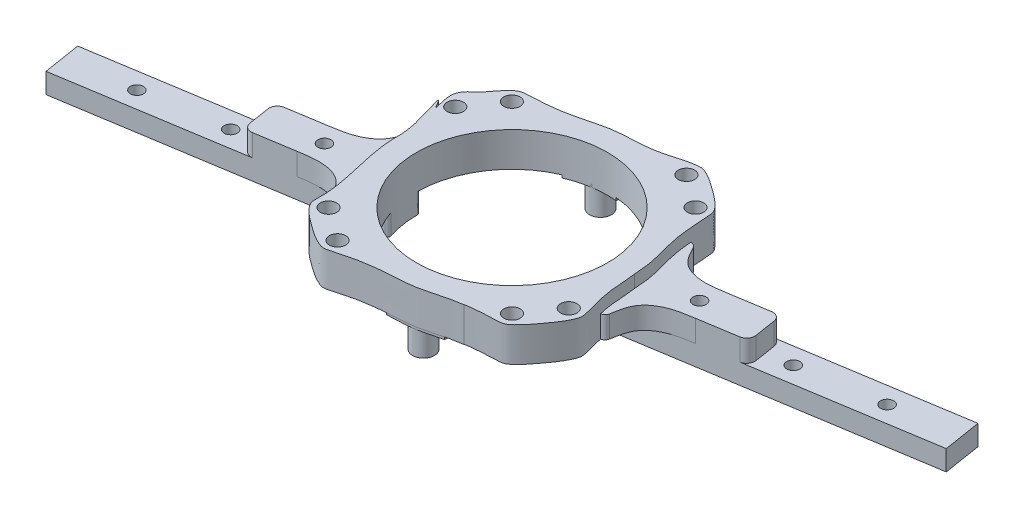
SolidWorks part; units mm, degrees
ref_plane "前视基准面" through (0, 0, 0) normal (0, 0, 1) x (1, 0, 0)
ref_plane "上视基准面" through (0, 0, 0) normal (0, 1, 0) x (1, 0, 0)
ref_plane "右视基准面" through (0, 0, 0) normal (1, 0, 0) x (0, 0, -1)
sketch "草图1" plane through (0, 0, 0) normal (0, 1, 0) x (1, 0, 0)
  circle A0 centre (0, 0) radius 17.5
  circle A1 centre (0, 0) radius 18.901
  dimension "D1" = 35
extrude "凸台-拉伸1" add sketch "草图1" along normal blind 2
sketch "草图2" plane through (0, 0, 0) normal (0, -1, 0) x (1, 0, 0)
  circle A0 centre (-10.7739, 21.1656) radius 1.5
  circle A1 centre (16.8004, 16.7872) radius 1.5
  circle A2 centre (21.1656, 10.7739) radius 1.5
  circle A3 centre (16.7872, -16.8004) radius 1.5
  circle A4 centre (10.7739, -21.1656) radius 1.5
  circle A5 centre (-16.8004, -16.7872) radius 1.5
  circle A6 centre (-21.1656, -10.7739) radius 1.5
  circle A7 centre (-16.7872, 16.8004) radius 1.5
  circle A28 centre (0, 0) radius 17.5
  spline S3 degree 3 poles (11.007, 19.7796) (11.3114, 19.6784) (14.2307, 19.3249) (16.1426, 19.3879) (17.8124, 19.1708) (19.4344, 17.903) (21.2548, 15.4236) (23.0457, 12.9332) (23.7495, 10.9887) (23.274, 8.5261) (21.9734, 4.7628) (22.0269, 1.1873) (21.7447, -0.683) knots 0 0 0 0 0.101498 0.202996 0.236379 0.269761 0.41266 0.555558 0.58894 0.622323 0.811161 1 1 1 1
  spline S4 degree 3 poles (21.7447, -0.683) (21.6101, -1.5752) (21.6055, -3.3542) (20.6884, -6.8809) (19.4904, -11.3054) (19.4855, -15.3122) (19.178, -17.8032) (17.9056, -19.4334) (15.4365, -21.2528) (12.9718, -22.9922) (11.1783, -23.6905) (8.6855, -23.5473) (4.924, -21.9674) (0.2192, -21.8124) (-3.3386, -21.5662) (-6.4463, -20.811) (-9.0785, -20.0903) (-12.7412, -19.4848) (-15.1253, -19.3752) (-17.5836, -19.2474) (-19.4002, -18.127) (-20.9244, -15.1209) (-24.3676, -13.3124) (-22.2966, -7.7817) (-24.7387, -12.2711) (-21.435, -3.3276) (-22.0126, 0.3206) (-20.5515, 8.1406) (-19.1109, 13.0019) (-19.2816, 16.8284) knots 0 0 0 0 0.02817 0.053916 0.112305 0.168269 0.178162 0.188055 0.230405 0.272754 0.280796 0.288838 0.34856 0.404524 0.432694 0.45844 0.502911 0.516855 0.572819 0.576577 0.592462 0.634812 0.677161 0.707499 0.719914 0.775878 0.831843 0.888071 1 1 1 1
  spline S5 degree 3 poles (-19.2816, 16.8284) (-19.323, 17.5174) (-18.1907, 19.2578) (-15.4061, 21.2421) (-12.9273, 23.0421) (-10.9838, 23.7431) (-9.3566, 23.4387) (-7.2233, 22.7077) (-4.4614, 22.2162) (-1.8337, 21.8607) (0.7732, 21.7432) (3.3794, 21.5754) (7.3403, 20.5662) (8.6858, 20.19) (9.8558, 19.9936) (10.7406, 19.8682) (11.007, 19.7796) knots 0 0 0 0 0.047987 0.150696 0.253406 0.277399 0.301393 0.374345 0.447298 0.510152 0.573007 0.641327 0.709648 0.853023 0.882058 1 1 1 1
  dimension "D1" = 3
extrude "凸台-拉伸2" add sketch "草图2" along normal blind 4.3 and the other way blind 2
sketch "草图3" plane through (0, -4.3, 0) normal (0, -1, 0) x (1, 0, 0)
  line L0 (8.3212, 9.3102) -> (-43.6069, 17.5558) construction
  line L1 (3.0581, 19.2587) -> (0, 0) construction
  line L2 (0, 0) -> (-3.0579, -19.2577) construction
  line L3 (-8.4247, -9.2928) -> (43.5035, -17.5384) construction
  circle A0 centre (3.0581, 19.2587) radius 2
  circle A1 centre (3.0581, 19.2587) radius 9 construction
  circle A2 centre (-3.0579, -19.2577) radius 2
  circle A3 centre (-3.0579, -19.2577) radius 9 construction
  dimension "D1" = 18
  dimension "D2" = 4
  dimension "D3" = 18
  dimension "D4" = 4
extrude "凸台-拉伸3" add sketch "草图3" along normal blind 5
sketch "草图5" plane through (0, -4.3, 0) normal (0, -1, 0) x (1, 0, 0)
  line L0 (0, 0) -> (38.9853, -6.1904) construction
  line L1 (70.6703, -14.0546) -> (-71.5479, 8.5279) construction
  circle A0 centre (3.0581, 19.2587) radius 5 construction
  arc A1 (-1.5944, 17.4272) -> (6.9144, 16.0761) centre (0, 0) cw
  arc A2 (-2.6852, -17.2928) -> (2.7444, 17.2835) centre (0, 0) ccw construction
  arc A3 (-1.3158, 21.6815) -> (-1.5944, 17.4272) centre (3.0581, 19.2587) ccw
  arc A4 (7.9454, 20.3141) -> (6.9144, 16.0761) centre (3.0581, 19.2587) cw
  arc A5 (-7.9672, -20.2075) -> (-6.9144, -16.0761) centre (-3.0581, -19.2587) cw
  arc A6 (-6.9144, -16.0761) -> (1.5944, -17.4272) centre (0, 0) ccw
  arc A7 (1.262, -21.7761) -> (1.5944, -17.4272) centre (-3.0581, -19.2587) ccw
  spline S0 degree 3 poles (-1.3158, 21.6815) (-0.2135, 21.5939) (1.3807, 21.5885) (3.4585, 21.3907) (5.444, 20.9684) (6.9168, 20.5202) (7.9454, 20.3141) knots 0 0 0 0 0.352817 0.508743 0.665414 1 1 1 1
  spline S2 degree 3 poles (-7.9672, -20.2075) (-6.892, -20.4656) (-5.3746, -20.9543) (-3.3377, -21.4099) (-1.319, -21.6234) (0.2201, -21.6535) (1.262, -21.7761) knots 0 0 0 0 0.352817 0.508743 0.665414 1 1 1 1
  dimension "D1" = 10
extrude "凸台-拉伸5" add sketch "草图5" along normal blind 0.5
sketch "草图6" plane through (0, -4.3, 0) normal (0, -1, 0) x (1, 0, 0)
  line L0 (0, 0) -> (83.2876, -13.2251) construction
  line L1 (70.6703, -14.0546) -> (-71.5479, 8.5279) construction
  line L2 (0, 0) -> (7.0837, 44.6111) construction
  line L3 (22.6545, 6.4264) -> (16.7134, 7.3698)
  line L4 (32.0065, -1.5404) -> (39.048, -2.6585)
  line L5 (71.6577, -7.8366) -> (-70.5606, 14.746) construction
  line L6 (-30.9094, 8.4499) -> (-37.9509, 9.5679)
  line L7 (40.2942, -4.3752) -> (39.9809, -6.3485)
  line L8 (19.5496, -13.1279) -> (13.6084, -12.1845)
  line L9 (30.9094, -8.4499) -> (37.9509, -9.5679)
  line L10 (39.6675, -8.3217) -> (39.9809, -6.3485)
  line L11 (-39.6675, 8.3217) -> (-39.9809, 6.3485)
  line L12 (-40.2942, 4.3752) -> (-39.9809, 6.3485)
  line L13 (-32.0065, 1.5404) -> (-39.048, 2.6585)
  line L14 (-19.5496, 13.1279) -> (-13.6084, 12.1845)
  line L15 (-22.6545, -6.4264) -> (-16.7134, -7.3698)
  circle A0 centre (21.1656, 10.7739) radius 2.5 construction
  arc A1 (1.5944, -17.4272) -> (6.9144, 16.0761) centre (0, 0) ccw construction
  arc A2 (13.3066, -11.3659) -> (16.1729, 6.685) centre (0, 0) ccw
  arc A3 (23.4842, 5.6027) -> (22.6545, 6.4264) centre (22.4977, 5.4388) ccw
  arc A4 (16.7134, 7.3698) -> (16.1729, 6.685) centre (16.6349, 6.876) ccw
  arc A5 (39.048, -2.6585) -> (40.2942, -4.3752) centre (38.8128, -4.14) cw
  arc A6 (13.6084, -12.1845) -> (13.3066, -11.3659) centre (13.6868, -11.6907) cw
  arc A7 (20.5935, -12.6017) -> (19.5496, -13.1279) centre (19.7064, -12.1402) cw
  arc A8 (37.9509, -9.5679) -> (39.6675, -8.3217) centre (38.1861, -8.0865) ccw
  arc A9 (-37.9509, 9.5679) -> (-39.6675, 8.3217) centre (-38.1861, 8.0865) ccw
  arc A10 (-39.048, 2.6585) -> (-40.2942, 4.3752) centre (-38.8128, 4.14) cw
  arc A11 (-20.5935, 12.6017) -> (-19.5496, 13.1279) centre (-19.7064, 12.1402) cw
  arc A12 (-13.6084, 12.1845) -> (-13.3066, 11.3659) centre (-13.6868, 11.6907) cw
  arc A13 (-16.1729, -6.685) -> (-13.3066, 11.3659) centre (0, 0) cw
  arc A14 (-16.7134, -7.3698) -> (-16.1729, -6.685) centre (-16.6349, -6.876) ccw
  arc A15 (-23.4842, -5.6027) -> (-22.6545, -6.4264) centre (-22.6575, -5.5997) ccw
  spline S0 degree 3 poles (20.5935, -12.6017) (20.8165, -12.1731) (21.4171, -11.0059) (22.8603, -8.9685) (26.5188, -7.7575) (29.1956, -8.1777) (30.9094, -8.4499) knots 0.057026 0.057026 0.057026 0.057026 0.169435 0.36028 0.616457 1 1 1 1
  spline S1 degree 3 poles (23.4842, 5.6027) (23.5634, 5.1261) (23.7729, 3.8302) (24.514, 1.446) (27.6174, -0.8387) (30.2927, -1.2683) (32.0065, -1.5404) knots 0.057026 0.057026 0.057026 0.057026 0.169435 0.36028 0.616457 1 1 1 1
  spline S2 degree 3 poles (-23.4842, -5.6027) (-23.5634, -5.1261) (-23.7729, -3.8302) (-24.514, -1.446) (-27.6174, 0.8387) (-30.2927, 1.2683) (-32.0065, 1.5404) knots 0.057026 0.057026 0.057026 0.057026 0.169435 0.36028 0.616457 1 1 1 1
  spline S3 degree 3 poles (-20.5935, 12.6017) (-20.8165, 12.1731) (-21.4171, 11.0059) (-22.8603, 8.9685) (-26.5188, 7.7575) (-29.1956, 8.1777) (-30.9094, 8.4499) knots 0.057026 0.057026 0.057026 0.057026 0.169435 0.36028 0.616457 1 1 1 1
  point P34 (15.8047, 7.514)
  dimension "D1" = 5
  dimension "D2" = 1
  dimension "D3" = 0.5
  dimension "D4" = 1.5
extrude "凸台-拉伸6" add sketch "草图6" against normal blind 4 separate body
sketch "草图7" plane through (0, -4.3, 0) normal (0, -1, 0) x (1, 0, 0)
  line L0 (17.2287, -6.2775) -> (70.5606, -14.746)
  line L1 (17.2287, -6.2775) -> (18.3258, 0.6319) construction
  line L2 (70.5606, -14.746) -> (71.6577, -7.8366)
  line L3 (18.3258, 0.6319) -> (71.6577, -7.8366)
  line L4 (17.2287, -6.2775) -> (71.6577, -7.8366) construction
  line L5 (70.5606, -14.746) -> (18.3258, 0.6319) construction
  line L6 (71.6577, -7.8366) -> (-70.5606, 14.746) construction
  line L7 (71.6266, -8.0321) -> (70.5916, -14.5504) construction
  line L8 (18.3258, 0.6319) -> (18.0775, 0.6713)
  line L9 (17.2287, -6.2775) -> (16.9804, -6.2381)
  line L10 (70.5606, -14.746) -> (-71.6577, 7.8366) construction
  line L11 (0, 0) -> (5.947, 37.4527) construction
  line L12 (-71.6577, 7.8366) -> (-70.5606, 14.746)
  line L13 (-17.2287, 6.2775) -> (-70.5606, 14.746)
  line L14 (-18.3258, -0.6319) -> (-71.6577, 7.8366)
  line L15 (-18.3258, -0.6319) -> (-18.0775, -0.6713)
  line L16 (-17.2287, 6.2775) -> (-16.9804, 6.2381)
  arc A0 (1.5944, -17.4272) -> (6.9144, 16.0761) centre (0, 0) ccw construction
  arc A1 (17.4991, 0.1726) -> (16.585, -5.5847) centre (0, 0) cw
  arc A2 (16.9804, -6.2381) -> (16.585, -5.5847) centre (17.0588, -5.7443) cw
  arc A3 (18.0775, 0.6713) -> (17.4991, 0.1726) centre (17.9991, 0.1775) ccw
  arc A4 (-18.0775, -0.6713) -> (-17.4991, -0.1726) centre (-17.9991, -0.1775) ccw
  arc A5 (-16.9804, 6.2381) -> (-16.585, 5.5847) centre (-17.0588, 5.7443) cw
  arc A6 (-16.585, 5.5847) -> (-17.4991, -0.1726) centre (0, 0) ccw
  point P1 (44.4432, -7.057)
  point P20 (16.3861, -6.1437)
  point P23 (17.4832, 0.7657)
  dimension "D1" = 0.5
extrude "凸台-拉伸7" add sketch "草图7" along normal up to surface (3.7 mm away)
sketch "草图8" plane through (0, -8, 0) normal (0, -1, 0) x (1, 0, 0)
  circle A0 centre (59.2576, -9.4094) radius 1.2
  circle A1 centre (44.4432, -7.057) radius 1.2
  circle A2 centre (29.6288, -4.7047) radius 1.2
  circle A3 centre (-29.6288, 4.7047) radius 1.2
  circle A4 centre (-44.4432, 7.057) radius 1.2
  circle A5 centre (-59.2576, 9.4094) radius 1.2
  dimension "D1" = 2.4
extrude "切除-拉伸1" cut sketch "草图8" against normal through all
